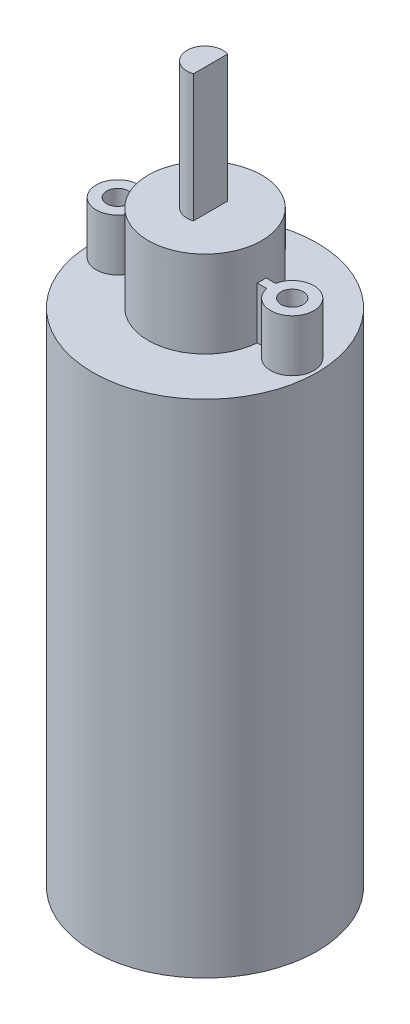
SolidWorks part; units mm, degrees
ref_plane "Front Plane" through (0, 0, 0) normal (0, 0, 1) x (1, 0, 0)
ref_plane "Top Plane" through (0, 0, 0) normal (0, 1, 0) x (1, 0, 0)
ref_plane "Right Plane" through (0, 0, 0) normal (1, 0, 0) x (0, 0, -1)
sketch "Sketch1" plane through (0, 0, 0) normal (0, 1, 0) x (1, 0, 0)
  circle A0 centre (0, 0) radius 10.287
  dimension "D1" = 20.574
extrude "Boss-Extrude1" add sketch "Sketch1" along normal blind 45.974
sketch "Sketch2" plane through (0, 45.974, 0) normal (0, 1, 0) x (1, 0, 0)
  circle A0 centre (0, 0) radius 5.207
  dimension "D1" = 10.414
extrude "Boss-Extrude2" add sketch "Sketch2" along normal blind 7.9375
sketch "Sketch3" plane through (0, 53.9115, 0) normal (0, 1, 0) x (1, 0, 0)
  circle A0 centre (0, 0) radius 1.651
  dimension "D1" = 3.302
extrude "Boss-Extrude3" add sketch "Sketch3" along normal blind 11.684
sketch "Sketch4" plane through (0, 45.974, 0) normal (0, 1, 0) x (1, 0, 0)
  line L0 (-8.001, 0) -> (8.001, 0) construction
  line L2 (-6.4626, 0.405) -> (6.4948, 0.405)
  line L3 (-6.4626, 0.405) -> (-6.4626, -0.405)
  line L4 (-6.4626, -0.405) -> (6.4948, -0.405)
  line L5 (6.4948, 0.405) -> (6.4948, -0.405)
  circle A1 centre (-8.001, 0) radius 1.9844
  circle A2 centre (8.001, 0) radius 1.9844
  circle A3 centre (-8.001, 0) radius 1.016
  circle A4 centre (8.001, 0) radius 1.016
  point P2 (0, 0)
  point P14 (-6.4626, 0)
  circle M8 centre (0, 0) radius 5.207
  dimension "D2" = 3.9688
  dimension "D3" = 2.032
  dimension "D1" = 16.002
  dimension "D4" = 0.81
  dimension "D5" = 12.9574
  dimension "D6" = 6.4626
extrude "Boss-Extrude5" add sketch "Sketch4" along normal blind 4.7625 contours A1 L0 L2 M8 | L0 A1 L4 M8 | L0 L3 L4 A1 | L3 L0 A1 L2 | A3 L3 L2 A1 L4 | A2 L0 L5 L2 | L0 A2 L2 M8 | L0 L4 A2 M8 | L0 A2 L4 L5 | L4 A2 L2 L5 A4 region at (-6.5184, 45.974, 0.2025) region at (-6.2464, 45.974, -0.1992) region at (-6.2464, 45.974, 0.1992) region at (-5.6162, 45.974, -0.2048) region at (-5.6162, 45.974, 0.2048) region at (5.6162, 45.974, -0.2048) region at (5.6162, 45.974, 0.2048) region at (6.2625, 45.974, -0.1995) region at (6.2625, 45.974, 0.1995) region at (6.5507, 45.974, -0.2025)
sketch "Sketch5" plane through (0, 65.5955, 0) normal (0, 1, 0) x (1, 0, 0)
  line L0 (0.508, 1.5709) -> (0.508, -1.5709)
  circle A0 centre (0, 0) radius 1.651 construction
  circle A2 centre (0, 0) radius 1.651
  circle M2 centre (0, 0) radius 1.651
  dimension "D1" = 0.508
extrude "Cut-Extrude1" cut sketch "Sketch5" against normal up to surface (11.684 mm away) contours L0 M2 region at (0.9822, 65.5955, 0) up to face at (0, 53.9115, 1.651)
equation "\"motor diamiter\"= 20.65mm"
equation "\"little diamiter\"= 10.3mm"
equation "\"shaft diamiter\"= 3.34mm"
equation "\"hole spacing\"= 16mm"
equation "\"hole size\"= 2mm'probobly"
equation "\"hole stickout\"= 3 / 16in"
equation "\"small diamiter length\"= 5 / 16in"
equation "\"Outer Hole size\"= 5 / 32"
equation "\"length\"= 46.05mm"
equation "\"D1@Sketch1\"=\"motor diamiter\""
equation "\"D1@Boss-Extrude1\"=\"length\""
equation "\"D1@Sketch2\"=\"little diamiter\""
equation "\"D1@Boss-Extrude2\"=\"small diamiter length\""
equation "\"D1@Sketch3\"=\"shaft diamiter\""
equation "\"shaft length\"= 11.7mm"
equation "\"D1@Boss-Extrude3\"=\"shaft length\""
equation "\"D1@Sketch4\"=\"hole spacing\""
equation "\"D2@Sketch4\"=\"Outer Hole size\""
equation "\"D3@Sketch4\"=\"hole size\""
equation "\"D1@Boss-Extrude5\"=\"hole stickout\""
